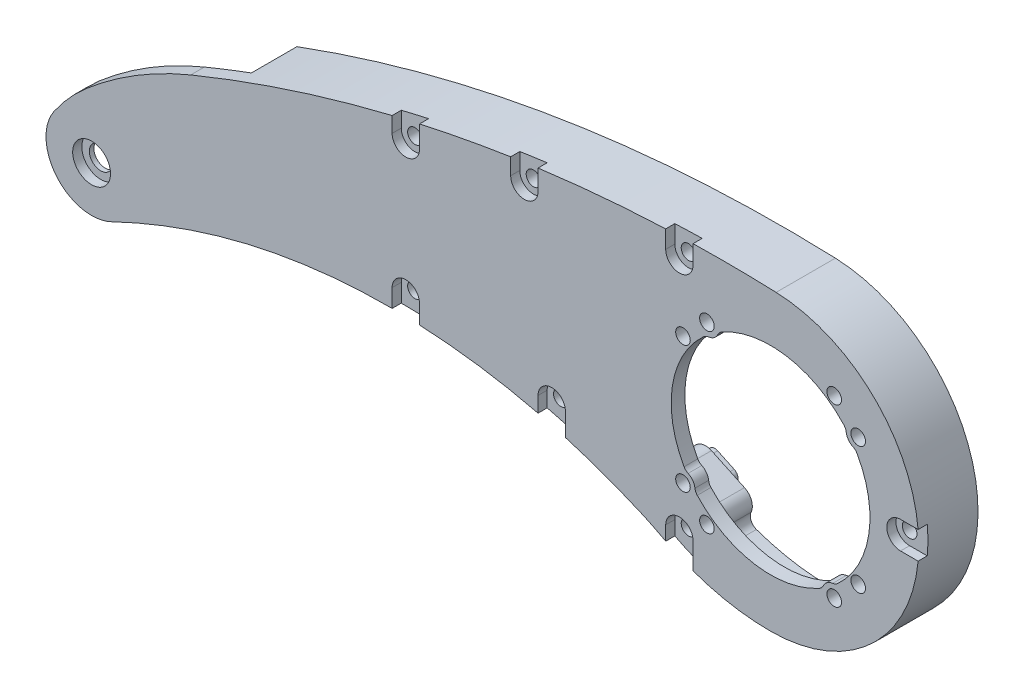
SolidWorks part; units mm, degrees
material "6061-T6 (SS)"
ref_plane "前视基准面" through (0, 0, 0) normal (0, 0, 1) x (1, 0, 0)
ref_plane "上视基准面" through (0, 0, 0) normal (0, 1, 0) x (1, 0, 0)
ref_plane "右视基准面" through (0, 0, 0) normal (1, 0, 0) x (0, 0, -1)
other "Configuration Table"
sketch "草图1" plane through (0, 0, 0) normal (0, 0, 1) x (1, 0, 0)
  line L0 (-74.3846, 0) -> (17.4339, 0) construction
  line L1 (0, 31.8895) -> (0, -25.7876) construction
  line L2 (0, 0) -> (19.2142, 13.9599) construction
  line L3 (0, 0) -> (13.9599, 19.2142) construction
  line L4 (0, 0) -> (-148.9161, -18) construction
  line L6 (0, 0) -> (-1.2281, 22.9672) construction
  line L8 (-1.2281, 22.9672) -> (-150.1441, 4.9672) construction
  line L9 (-150.1441, 4.9672) -> (-148.9161, -18) construction
  line L10 (-148.9161, -18) -> (-97.5528, -158.9319)
  line L12 (0, 0) -> (-103.1063, -167.9797) construction
  arc A116 (16.0762, 14.724) -> (-10.7394, 18.9712) centre (0, 0) ccw
  circle A117 centre (0, 0) radius 23.75 construction
  circle A118 centre (19.2142, 13.9599) radius 1.6
  circle A119 centre (13.9599, 19.2142) radius 1.6
  circle A120 centre (19.2142, -13.9599) radius 1.6
  circle A121 centre (13.9599, -19.2142) radius 1.6
  circle A122 centre (-13.9599, -19.2142) radius 1.6
  circle A123 centre (-19.2142, -13.9599) radius 1.6
  circle A124 centre (-19.2142, 13.9599) radius 1.6
  circle A125 centre (-13.9599, 19.2142) radius 1.6
  arc A126 (0, -32.5) -> (1.2171, 32.4772) centre (0, 0) ccw
  arc A127 (-157.1671, -12.3502) -> (-144.5702, -27.0063) centre (-148.9161, -18) ccw
  arc A134 (-28.3708, -24.2609) -> (-127.3793, -19.9637) centre (-83.3912, -149.2082) ccw
  arc A135 (-127.3793, -19.9637) -> (-144.5702, -27.0063) centre (-78.0965, -164.7651) ccw
  arc A136 (1.2171, 32.4772) -> (-127.1723, 9.5805) centre (-10.2849, -274.4361) ccw
  arc A138 (-23.6381, -26.5665) -> (-28.3708, -24.2609) centre (-55.9067, -86.7929) ccw
  arc A139 (0, -32.5) -> (-23.6381, -26.5665) centre (0, 17.5518) cw
  arc A140 (16.5853, 13.6255) -> (18.0838, 11.5631) centre (19.2142, 13.9599) ccw
  arc A141 (16.5853, 13.6255) -> (16.0762, 14.724) centre (14.6013, 13.3732) ccw
  arc A142 (18.0838, 11.5631) -> (18.9712, 10.7394) centre (17.2307, 9.7541) cw
  arc A143 (11.5631, -18.0838) -> (10.7394, -18.9712) centre (9.7541, -17.2307) cw
  arc A144 (13.6255, -16.5853) -> (11.5631, -18.0838) centre (13.9599, -19.2142) ccw
  arc A145 (13.6255, -16.5853) -> (14.724, -16.0762) centre (13.3732, -14.6013) ccw
  arc A146 (-18.0838, -11.5631) -> (-18.9712, -10.7394) centre (-17.2307, -9.7541) cw
  arc A147 (-16.5853, -13.6255) -> (-18.0838, -11.5631) centre (-19.2142, -13.9599) ccw
  arc A148 (-16.5853, -13.6255) -> (-16.0762, -14.724) centre (-14.6013, -13.3732) ccw
  arc A149 (-11.5631, 18.0838) -> (-10.7394, 18.9712) centre (-9.7541, 17.2307) cw
  arc A150 (-13.6255, 16.5853) -> (-11.5631, 18.0838) centre (-13.9599, 19.2142) ccw
  arc A151 (-13.6255, 16.5853) -> (-14.724, 16.0762) centre (-13.3732, 14.6013) ccw
  arc A152 (-16.0762, -14.724) -> (10.7394, -18.9712) centre (0, 0) ccw
  arc A153 (14.724, -16.0762) -> (18.9712, 10.7394) centre (0, 0) ccw
  arc A154 (-14.724, 16.0762) -> (-18.9712, -10.7394) centre (0, 0) ccw
  arc A155 (-127.1723, 9.5805) -> (-150.1438, -4.5112) centre (-94.9478, -68.7195) ccw
  arc A156 (-150.1438, -4.5112) -> (-157.1671, -12.3502) centre (-123.7132, -35.2574) ccw
  arc A157 (11.5631, 18.0838) -> (10.7394, 18.9712) centre (9.7541, 17.2307) ccw
  arc A158 (11.5631, 18.0838) -> (13.6255, 16.5853) centre (13.9599, 19.2142) ccw
  arc A159 (13.6255, 16.5853) -> (14.724, 16.0762) centre (13.3732, 14.6013) cw
  arc A160 (16.5853, -13.6255) -> (16.0762, -14.724) centre (14.6013, -13.3732) cw
  arc A161 (18.0838, -11.5631) -> (16.5853, -13.6255) centre (19.2142, -13.9599) ccw
  arc A162 (18.0838, -11.5631) -> (18.9712, -10.7394) centre (17.2307, -9.7541) ccw
  arc A163 (-13.6255, -16.5853) -> (-14.724, -16.0762) centre (-13.3732, -14.6013) cw
  arc A164 (-11.5631, -18.0838) -> (-13.6255, -16.5853) centre (-13.9599, -19.2142) ccw
  arc A165 (-11.5631, -18.0838) -> (-10.7394, -18.9712) centre (-9.7541, -17.2307) ccw
  arc A166 (-16.5853, 13.6255) -> (-16.0762, 14.724) centre (-14.6013, 13.3732) cw
  arc A167 (-18.0838, 11.5631) -> (-16.5853, 13.6255) centre (-19.2142, 13.9599) ccw
  arc A168 (-18.0838, 11.5631) -> (-18.9712, 10.7394) centre (-17.2307, 9.7541) ccw
  arc A169 (18.9712, 10.7394) -> (16.0762, 14.724) centre (0, 0) ccw
  arc A170 (-10.7394, 18.9712) -> (-14.724, 16.0762) centre (0, 0) ccw
  arc A171 (10.7394, -18.9712) -> (14.724, -16.0762) centre (0, 0) ccw
  point P27 (0, 0)
  point P73 (0, 0)
  point P83 (0, 0)
  point P105 (0, 0)
  dimension "D1" = 43.6
  dimension "D3" = 36
  dimension "D4" = 3.2
  dimension "D2" = 47.5
  dimension "D6" = 3.2
  dimension "D8" = 65
  dimension "D15" = 20
  dimension "D16" = 5.3
  dimension "D17" = 2
  dimension "D5" = 18
  dimension "D9" = 18
  dimension "D10" = 150
  dimension "D11" = 23
  dimension "D12" = 150
  dimension "D13" = 103.132
  dimension "D14" = 51.566
  dimension "D19" = 2
  dimension "D7" = 4
  dimension "D18" = 4
  dimension "D20" = 4
extrude "凸台-拉伸1" add sketch "草图1" along normal blind 3 contours A135 A134 A138 A126 A127 A125 A124 A123 A122 A121 A120 A119 A118 A116 | A149 A170 A151 A150 | A142 A169 A141 A140 | A143 A171 A145 A144 region at (17.4035, 12.6444, 0) region at (-12.6444, 17.4035, 0) region at (12.6444, -17.4035, 0) region at (-60.0693, 1.6089, 0)
sketch "草图2" plane through (0, 0, 0) normal (0, 0, -1) x (-1, 0, 0)
  line L0 (-28.5, 0) -> (0, 0) construction
  line L2 (0, 0) -> (18.5599, 13.5842) construction
  line L3 (18.5599, 13.5842) -> (167.476, -4.4158) construction
  line L4 (167.476, -4.4158) -> (148.9161, -18) construction
  line L5 (148.9161, -18) -> (10.6983, -76.2738) construction
  line L7 (25.351, 15.2815) -> (162.3611, -1.2794) construction
  line L9 (24.751, 10.3176) -> (161.7611, -6.2433) construction
  line L11 (19.8643, 25.54) -> (27.8561, 25.1781)
  line L13 (18.7235, -21.0787) -> (25.9631, -17.6745)
  line L16 (53.5282, 22.5613) -> (61.4287, 21.3032)
  line L17 (79.2716, 17.6568) -> (87.0322, 15.7143)
  line L19 (80.013, -5.7241) -> (88.0129, -5.7588)
  line L20 (47.3274, -10.2892) -> (55.1237, -8.4956)
  arc A111 (-1.1422, 30.4786) -> (-30.0624, 5.1483) centre (0, 0) ccw
  arc A112 (0, -30.5) -> (16.1065, -27.7202) centre (0, 17.5518) ccw
  arc A114 (75.0886, -10.9322) -> (61.0732, -12.4928) centre (83.3912, -149.2082) ccw
  arc A115 (106.3649, -12.407) -> (93.2856, -10.553) centre (78.0965, -164.7651) ccw
  arc A116 (144.5702, -27.0063) -> (157.1671, -12.3502) centre (148.9161, -18) ccw
  arc A118 (157.1671, -12.3502) -> (150.1438, -4.5112) centre (123.7132, -35.2574) ccw
  arc A119 (127.1723, 9.5805) -> (-1.2171, 32.4772) centre (10.2849, -274.4361) ccw
  arc A120 (-1.2171, 32.4772) -> (0, -32.5) centre (0, 0) ccw
  arc A121 (-1.0673, 28.48) -> (0, -28.5) centre (0, 0) ccw construction
  arc A122 (0, -32.5) -> (23.6381, -26.5665) centre (0, 17.5518) ccw
  arc A123 (28.3708, -24.2609) -> (23.6381, -26.5665) centre (55.9067, -86.7929) ccw
  arc A124 (127.3793, -19.9637) -> (28.3708, -24.2609) centre (83.3912, -149.2082) ccw
  arc A125 (144.5702, -27.0063) -> (127.3793, -19.9637) centre (78.0965, -164.7651) ccw
  arc A126 (144.5702, -27.0063) -> (157.1671, -12.3502) centre (148.9161, -18) ccw
  arc A128 (127.1723, 9.5805) -> (-1.2171, 32.4772) centre (10.2849, -274.4361) ccw
  arc A129 (-1.2171, 32.4772) -> (0, -32.5) centre (0, 0) ccw
  arc A130 (0, -32.5) -> (23.6381, -26.5665) centre (0, 17.5518) ccw
  arc A131 (28.3708, -24.2609) -> (23.6381, -26.5665) centre (55.9067, -86.7929) ccw
  arc A132 (127.3793, -19.9637) -> (28.3708, -24.2609) centre (83.3912, -149.2082) ccw
  arc A133 (144.5702, -27.0063) -> (127.3793, -19.9637) centre (78.0965, -164.7651) ccw
  arc A134 (0, -28.5) -> (21.749, -23.0407) centre (0, 17.5518) ccw construction
  arc A135 (26.7587, -20.6001) -> (21.749, -23.0407) centre (55.9067, -86.7929) ccw construction
  arc A136 (128.6681, -16.177) -> (26.7587, -20.6001) centre (83.3912, -149.2082) ccw construction
  arc A137 (146.3086, -23.4038) -> (128.6681, -16.177) centre (78.0965, -164.7651) ccw construction
  arc A138 (146.3086, -23.4038) -> (153.7238, -14.4104) centre (148.9161, -18) ccw construction
  arc A139 (153.7238, -14.4104) -> (126.0955, 5.6977) centre (120.8678, -30.5198) ccw construction
  arc A140 (126.0955, 5.6977) -> (-1.0673, 28.48) centre (10.2849, -274.4361) ccw construction
  arc A141 (-28.3421, -2.9958) -> (-28.3421, 2.9958) centre (-28.5, 0) ccw
  arc A142 (-28.3421, 2.9958) -> (-30.0624, 5.1483) centre (-28.2451, 4.837) cw
  arc A143 (-28.3421, -2.9958) -> (-30.0624, -5.1483) centre (-28.2451, -4.837) ccw
  arc A144 (-30.0624, -5.1483) -> (0, -30.5) centre (0, 0) ccw
  circle A145 centre (-28.5, 0) radius 1.6
  arc A146 (-1.1422, 30.4786) -> (0, -30.5) centre (0, 0) ccw construction
  circle A147 centre (18.5599, 13.5842) radius 7 construction
  circle A148 centre (167.476, -4.4158) radius 6 construction
  arc A149 (17.0011, 28.6182) -> (19.8643, 25.54) centre (20, 28.5369) ccw
  arc A150 (27.8561, 25.1781) -> (30.9858, 27.985) centre (27.9918, 28.175) ccw
  arc A151 (17.0011, 28.6182) -> (15.0491, 30.6555) centre (15.0181, 28.672) ccw
  arc A152 (30.9858, 27.985) -> (33.1139, 29.8374) centre (32.9655, 27.8593) cw
  arc A153 (15.0491, 30.6555) -> (-1.1422, 30.4786) centre (10.2849, -274.4361) ccw
  circle A154 centre (20, 28.5369) radius 1.6
  arc A155 (126.6313, 7.6402) -> (-1.1422, 30.4786) centre (10.2849, -274.4361) ccw construction
  arc A156 (17.2617, -25.019) -> (18.7235, -21.0787) centre (20, -23.7935) cw
  arc A157 (25.9631, -17.6745) -> (30.0023, -19.2201) centre (27.2396, -20.3894) cw
  circle A158 centre (20, -23.7935) radius 1.6
  arc A159 (17.2617, -25.019) -> (16.1065, -27.7202) centre (15.4362, -25.8359) cw
  arc A160 (30.0023, -19.2201) -> (32.6241, -20.3211) centre (31.8778, -18.4263) ccw
  circle A161 centre (54, 25.524) radius 1.6
  arc A162 (27.5648, -22.4305) -> (22.6935, -24.8036) centre (55.9067, -86.7929) ccw construction
  arc A163 (0, -30.5) -> (22.6935, -24.8036) centre (0, 17.5518) ccw construction
  arc A164 (128.0237, -18.0703) -> (27.5648, -22.4305) centre (83.3912, -149.2082) ccw construction
  arc A165 (51.0293, 25.9419) -> (53.5282, 22.5613) centre (54, 25.524) ccw
  arc A166 (61.4287, 21.3032) -> (64.8541, 23.7404) centre (61.9005, 24.2659) ccw
  arc A167 (51.0293, 25.9419) -> (49.3187, 28.1856) centre (49.0649, 26.2183) ccw
  arc A168 (64.8541, 23.7404) -> (67.177, 25.3419) centre (66.8071, 23.393) cw
  arc A169 (49.3187, 28.1856) -> (33.1139, 29.8374) centre (10.2849, -274.4361) ccw
  circle A170 centre (80, 20.567) radius 1.6
  arc A171 (77.077, 21.2425) -> (79.2716, 17.6568) centre (80, 20.567) ccw
  arc A172 (87.0322, 15.7143) -> (90.6571, 17.8435) centre (87.7606, 18.6246) ccw
  arc A173 (77.077, 21.2425) -> (75.5687, 23.6269) centre (75.1443, 21.6892) ccw
  arc A175 (75.5687, 23.6269) -> (67.177, 25.3419) centre (10.2849, -274.4361) ccw
  circle A176 centre (48, -13.2128) radius 1.6
  circle A177 centre (80, -8.7241) radius 1.6
  arc A178 (45.1049, -13.9993) -> (47.3274, -10.2892) centre (48, -13.2128) cw
  arc A180 (45.1049, -13.9993) -> (43.7228, -16.4844) centre (43.1397, -14.5332) cw
  arc A182 (43.7228, -16.4844) -> (32.6241, -20.3211) centre (83.3912, -149.2082) ccw
  arc A183 (77.0018, -8.8285) -> (80.013, -5.7241) centre (80, -8.7241) cw
  arc A184 (88.0129, -5.7588) -> (90.9699, -8.3356) centre (87.9999, -8.7587) cw
  arc A185 (77.0018, -8.8285) -> (75.0886, -10.9322) centre (74.9666, -8.8993) cw
  arc A186 (90.9699, -8.3356) -> (93.2856, -10.553) centre (93.54, -7.9695) ccw
  arc A187 (106.3649, -12.407) -> (107.9278, -14.9061) centre (106, -14.3735) cw
  arc A188 (145.4394, -25.205) -> (128.0237, -18.0703) centre (78.0965, -164.7651) ccw construction
  arc A190 (145.4394, -25.205) -> (155.4422, -13.3729) centre (148.9161, -18) ccw construction
  arc A191 (75.5687, 23.6269) -> (93.1109, 19.2362) centre (10.2849, -274.4361) cw construction
  arc A192 (90.6571, 17.8435) -> (93.1109, 19.2362) centre (92.5724, 17.327) cw
  arc A193 (155.4422, -13.3729) -> (126.6313, 7.6402) centre (120.8678, -30.5198) ccw construction
  arc A194 (15.0491, 30.6555) -> (33.1139, 29.8374) centre (10.2849, -274.4361) cw construction
  arc A195 (49.3187, 28.1856) -> (67.177, 25.3419) centre (10.2849, -274.4361) cw construction
  arc A196 (93.1109, 19.2362) -> (114.3181, 12.4099) centre (10.2849, -274.4361) cw
  arc A197 (114.3181, 12.4099) -> (116.8779, 13.6021) centre (115, 14.2901) ccw
  arc A198 (55.1237, -8.4956) -> (58.7441, -10.8615) centre (55.7963, -11.4192) cw
  arc A199 (58.7441, -10.8615) -> (61.0732, -12.4928) centre (60.745, -10.4829) ccw
  arc A200 (127.3793, -19.9637) -> (28.3708, -24.2609) centre (83.3912, -149.2082) ccw construction
  arc A207 (157.1671, -12.3502) -> (127.1723, 9.5805) centre (120.8678, -30.5198) ccw construction
  arc A208 (157.1671, -12.3502) -> (150.1438, -4.5112) centre (123.7132, -35.2574) ccw
  arc A209 (150.1438, -4.5112) -> (127.1723, 9.5805) centre (94.9478, -68.7195) ccw
  arc A210 (150.1438, -4.5112) -> (127.1723, 9.5805) centre (94.9478, -68.7195) ccw
  point P113 (16.5105, -418.9921)
  point P135 (0, 0)
  point P136 (117.9242, -17.1228)
  arc M20 (127.1723, 9.5805) -> (-1.2171, 32.4772) centre (10.2849, -274.4361) ccw
  arc M21 (-1.2171, 32.4772) -> (0, -32.5) centre (0, 0) ccw
  arc M22 (0, -32.5) -> (23.6381, -26.5665) centre (0, 17.5518) ccw
  arc M23 (23.6381, -26.5665) -> (28.3708, -24.2609) centre (55.9067, -86.7929) cw
  arc M24 (28.3708, -24.2609) -> (127.3793, -19.9637) centre (83.3912, -149.2082) cw
  arc M25 (127.3793, -19.9637) -> (144.5702, -27.0063) centre (78.0965, -164.7651) cw
  dimension "D7" = 150
  dimension "D9" = 14
  dimension "D11" = 12
  dimension "D12" = 150
  dimension "D13" = 8
  dimension "D10" = 2.5
  dimension "D8" = 166.66
  dimension "D14" = 20
  dimension "D15" = 8
  dimension "D16" = 8
  dimension "D17" = 8
  dimension "D18" = 54
  dimension "D19" = 80
  dimension "D20" = 8
  dimension "D21" = 48
  dimension "D22" = 80
  dimension "D23" = 8
  dimension "D6" = 23
  dimension "D25" = 106
  dimension "D26" = 2
  dimension "D27" = 115
  dimension "D28" = 20
  dimension "D4" = 6
  dimension "D5" = 3.2
  dimension "D24" = 2
  dimension "D1" = 0
  dimension "D2" = 2
  dimension "D3" = 2
extrude "凸台-拉伸2" add sketch "草图2" along normal blind 10 contours M20 M21 M22 M23 M24 M25 region at (-17.9227, 26.6047, 0)
sketch "草图4" plane through (0, 0, -10) normal (0, 0, -1) x (-1, 0, 0)
  line L0 (20, 28.5369) -> (27.9918, 28.175) construction
  line L3 (61.9005, 24.2659) -> (54, 25.524) construction
  line L8 (80, 20.567) -> (87.7606, 18.6246) construction
  line L9 (20, -23.7935) -> (27.2396, -20.3894) construction
  line L10 (48, -13.2128) -> (55.7963, -11.4192) construction
  line L11 (80, -8.7241) -> (87.9999, -8.7587) construction
  line L12 (27.2396, -20.3894) -> (23.6198, -22.0915) construction
  line L15 (27.8779, -21.7468) -> (24.2581, -23.4489)
  line L24 (26.6013, -19.032) -> (22.9815, -20.734)
  line L27 (27.9918, 28.175) -> (23.9959, 28.356) construction
  line L30 (27.924, 26.6766) -> (23.9281, 26.8575)
  line L33 (28.0597, 29.6735) -> (24.0638, 29.8545)
  line L36 (61.9005, 24.2659) -> (57.9502, 24.8949) construction
  line L39 (87.7606, 18.6246) -> (83.8803, 19.5958) construction
  line L40 (87.3964, 17.1695) -> (83.5161, 18.1407)
  line L41 (88.1248, 20.0797) -> (84.2445, 21.0509)
  line L42 (87.9999, -8.7587) -> (84, -8.7414) construction
  line L43 (87.9934, -10.2587) -> (83.9935, -10.2414)
  line L44 (88.0064, -7.2587) -> (84.0065, -7.2414)
  line L45 (55.7963, -11.4192) -> (51.8982, -12.316) construction
  line L46 (56.1326, -12.881) -> (52.2345, -13.7778)
  line L47 (55.46, -9.9574) -> (51.5619, -10.8542)
  line L48 (61.6646, 22.7845) -> (57.7143, 23.4136)
  line L49 (62.1363, 25.7472) -> (58.1861, 26.3763)
  arc A24 (27.8779, -21.7468) -> (26.6013, -19.032) centre (27.2396, -20.3894) ccw
  arc A25 (22.9815, -20.734) -> (24.2581, -23.4489) centre (23.6198, -22.0915) ccw
  arc A26 (27.924, 26.6766) -> (28.0597, 29.6735) centre (27.9918, 28.175) ccw
  arc A27 (24.0638, 29.8545) -> (23.9281, 26.8575) centre (23.9959, 28.356) ccw
  arc A30 (87.3964, 17.1695) -> (88.1248, 20.0797) centre (87.7606, 18.6246) ccw
  arc A31 (84.2445, 21.0509) -> (83.5161, 18.1407) centre (83.8803, 19.5958) ccw
  arc A32 (87.9934, -10.2587) -> (88.0064, -7.2587) centre (87.9999, -8.7587) ccw
  arc A33 (84.0065, -7.2414) -> (83.9935, -10.2414) centre (84, -8.7414) ccw
  arc A34 (56.1326, -12.881) -> (55.46, -9.9574) centre (55.7963, -11.4192) ccw
  arc A35 (51.5619, -10.8542) -> (52.2345, -13.7778) centre (51.8982, -12.316) ccw
  arc A36 (61.6646, 22.7845) -> (62.1363, 25.7472) centre (61.9005, 24.2659) ccw
  arc A37 (58.1861, 26.3763) -> (57.7143, 23.4136) centre (57.9502, 24.8949) ccw
  point P12 (25.4297, -21.2404)
  point P18 (25.9939, 28.2655)
  point P24 (59.9253, 24.5804)
  point P30 (85.8204, 19.1102)
  point P36 (85.9999, -8.7501)
  point P42 (53.8473, -11.8676)
  dimension "D2" = 1.5
  dimension "D1" = 4
extrude "凸台-拉伸3" add sketch "草图4" along normal blind 2 contours L44 A33 L43 A32 | L33 A27 L30 A26 | L49 A37 L48 A36 | A30 L41 A31 L40 | A34 L47 A35 L46 | A24 L24 A25 L15 region at (-85.9999, -8.7501, -10)
sketch "草图5" plane through (0, 0, -10) normal (0, 0, -1) x (-1, 0, 0)
  circle A0 centre (80, -8.7241) radius 1.6 construction
  circle A2 centre (-28.5, 0) radius 1.6 construction
  circle A4 centre (-28.5, 0) radius 1.6
  circle A6 centre (54, 25.524) radius 1.6 construction
  circle A8 centre (80, 20.567) radius 1.6 construction
  circle A10 centre (80, -8.7241) radius 1.6
  circle A12 centre (48, -13.2128) radius 1.6 construction
  circle A14 centre (20, -23.7935) radius 1.6 construction
  circle A27 centre (20, 28.5369) radius 1.6 construction
  circle A28 centre (54, 25.524) radius 1.6
  circle A29 centre (80, 20.567) radius 1.6
  circle A31 centre (48, -13.2128) radius 1.6
  circle A32 centre (20, -23.7935) radius 1.6
  circle A33 centre (20, 28.5369) radius 1.6
extrude "切除-拉伸1" cut sketch "草图5" against normal up to next
sketch "草图10" plane through (0, 0, 0) normal (0, 0, -1) x (-1, 0, 0)
  circle A0 centre (148.9161, -18) radius 2.5
  dimension "D1" = 5
extrude "切除-拉伸4" cut sketch "草图10" against normal up to next
sketch "草图11" plane through (0, 0, 3) normal (0, 0, 1) x (1, 0, 0)
  circle A0 centre (-148.9161, -18) radius 4.15
  dimension "D1" = 8.3
extrude "切除-拉伸5" cut sketch "草图11" against normal blind 2
sketch "草图13" plane through (0, 0, 3) normal (0, 0, 1) x (1, 0, 0)
  line L0 (-83, 20.567) -> (-83, 23.9606)
  line L1 (-77, 20.567) -> (-77, 25.3591)
  line L2 (-57, 25.524) -> (-57, 29.1191)
  line L3 (-51, 25.524) -> (-51, 29.982)
  line L4 (-23, 28.5369) -> (-23, 32.4293)
  line L5 (-17, 28.5369) -> (-17, 32.6192)
  line L6 (-83, -8.7241) -> (-83, -12.6837)
  line L7 (-77, -8.7241) -> (-77, -12.8328)
  line L8 (-51, -13.2128) -> (-51, -16.5813)
  line L9 (-45, -13.2128) -> (-45, -18.1922)
  line L10 (-23, -23.7935) -> (-23, -26.9025)
  line L11 (-17, -23.7935) -> (-17, -29.5246)
  line L12 (28.5, 3) -> (32.3612, 3)
  line L13 (28.5, -3) -> (32.3612, -3)
  line L14 (28.5, 3) -> (28.5, -3) construction
  arc A0 (-83, 20.567) -> (-77, 20.567) centre (-80, 20.567) ccw
  arc A1 (-57, 25.524) -> (-51, 25.524) centre (-54, 25.524) ccw
  arc A2 (-23, 28.5369) -> (-17, 28.5369) centre (-20, 28.5369) ccw
  arc A3 (28.5, 3) -> (28.5, -3) centre (28.5, 0) ccw
  arc A5 (-45, -13.2128) -> (-51, -13.2128) centre (-48, -13.2128) ccw
  arc A7 (-23.6381, -26.5665) -> (0, -32.5) centre (0, 17.5518) ccw construction
  arc A8 (1.2171, 32.4772) -> (-127.1723, 9.5805) centre (-10.2849, -274.4361) ccw construction
  arc A9 (-28.3708, -24.2609) -> (-127.3793, -19.9637) centre (-83.3912, -149.2082) ccw construction
  arc A10 (-23.6381, -26.5665) -> (0, -32.5) centre (0, 17.5518) ccw
  arc A11 (-23.6381, -26.5665) -> (-28.3708, -24.2609) centre (-55.9067, -86.7929) ccw construction
  arc A12 (0, -32.5) -> (1.2171, 32.4772) centre (0, 0) ccw construction
  arc A13 (1.2171, 32.4772) -> (-127.1723, 9.5805) centre (-10.2849, -274.4361) ccw
  arc A15 (0, -32.5) -> (1.2171, 32.4772) centre (0, 0) ccw
  arc A16 (-23.6381, -26.5665) -> (-28.3708, -24.2609) centre (-55.9067, -86.7929) ccw
  arc A18 (-17, -23.7935) -> (-23, -23.7935) centre (-20, -23.7935) ccw
  arc A19 (-28.3708, -24.2609) -> (-127.3793, -19.9637) centre (-83.3912, -149.2082) ccw
  arc A20 (-77, -8.7241) -> (-83, -8.7241) centre (-80, -8.7241) ccw
  circle M9 centre (28.5, 0) radius 1.6
  circle M10 centre (-54, 25.524) radius 1.6
  circle M11 centre (-80, 20.567) radius 1.6
  circle M12 centre (-80, -8.7241) radius 1.6
  circle M13 centre (-48, -13.2128) radius 1.6
  circle M14 centre (-20, -23.7935) radius 1.6
  circle M15 centre (-20, 28.5369) radius 1.6
  arc M17 (-127.3793, -19.9637) -> (-28.3708, -24.2609) centre (-83.3912, -149.2082) cw
  arc M19 (-23.6381, -26.5665) -> (0, -32.5) centre (0, 17.5518) ccw
  arc M20 (0, -32.5) -> (1.2171, 32.4772) centre (0, 0) ccw
  arc M21 (1.2171, 32.4772) -> (-127.1723, 9.5805) centre (-10.2849, -274.4361) ccw
  dimension "D1" = 6
  dimension "D2" = 6
  dimension "D3" = 3
  dimension "D4" = 6
extrude "切除-拉伸6" cut sketch "草图13" against normal blind 2 contours L9 A5 L8 M17 M13 | L11 A18 L10 M19 M14 | L12 L14 L13 M9 M20 | L14 A3 M9 | L4 A2 L5 M21 M15 | L2 A1 L3 M21 M10 | L0 A0 L1 M21 M11 | L7 A20 L6 M17 M12 region at (-79.9969, -12.6323, 3) region at (-47.9649, -17.2562, 3) region at (-20.0005, -28.2147, 3) region at (30.7421, 0, 3) region at (-19.9975, 32.4462, 3) region at (-53.9885, 29.4706, 3) region at (-82.9017, 22.2638, 3) region at (28.4329, 2.3, 3)
sketch "草图14" plane through (0, 0, 0) normal (0, 0, -1) x (-1, 0, 0)
  circle A0 centre (148.9161, -18) radius 10
  circle A1 centre (148.9161, -18) radius 7
  dimension "D1" = 14
  dimension "D2" = 20
extrude "凸台-拉伸4" add sketch "草图14" along normal blind 1.5
